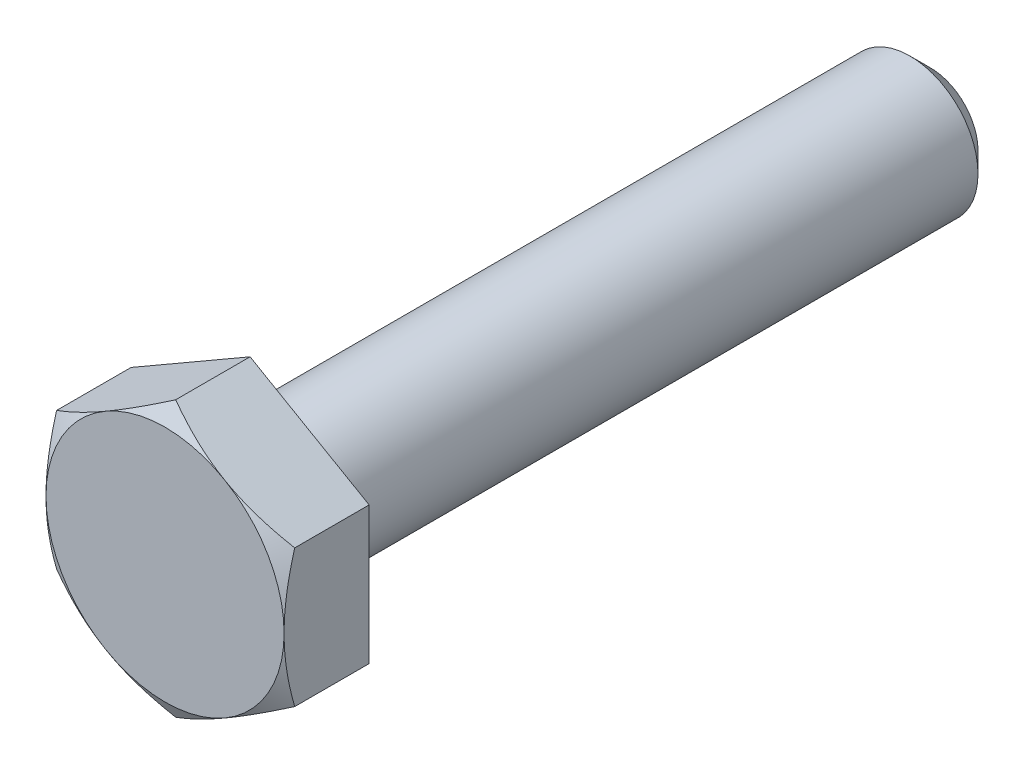
SolidWorks part; units mm, degrees
ref_plane "Front Plane" through (0, 0, 0) normal (0, 0, 1) x (1, 0, 0)
ref_plane "Top Plane" through (0, 0, 0) normal (0, 1, 0) x (1, 0, 0)
ref_plane "Right Plane" through (0, 0, 0) normal (1, 0, 0) x (0, 0, -1)
sketch "Sketch1" plane through (0, 0, 0) normal (1, 0, 0) x (0, 0, -1)
  line L0 (-17.8594, 0) -> (17.8594, 0) construction
  line L1 (-17.8594, 0) -> (-17.8594, 6.4158)
  line L2 (-17.8594, 6.4158) -> (-13.8906, 6.4158)
  line L3 (-13.8906, 6.4158) -> (-13.8906, 3.175)
  line L4 (-13.8906, 3.175) -> (17.8594, 3.175)
  line L5 (17.8594, 3.175) -> (17.8594, 0)
  line L6 (-17.8594, 5.5562) -> (-13.8906, 5.5562)
  line L7 (17.78, 3.3125) -> (18.415, 2.2126) construction
  line L8 (18.415, 2.2126) -> (19.05, 3.3125) construction
  line L9 (19.05, 3.3125) -> (17.78, 3.3125) construction
  line L10 (17.8594, 3.175) -> (18.9706, 3.175) construction
  line L11 (18.415, 3.3125) -> (18.415, 3.175) construction
  line L12 (18.415, 3.175) -> (18.415, 2.3501) construction
  line L13 (18.415, 2.3501) -> (18.415, 2.2126) construction
  line L14 (18.3356, 2.3501) -> (18.4944, 2.3501)
  line L15 (17.8197, 3.2437) -> (19.0103, 3.2437)
  line L16 (18.4944, 2.3501) -> (19.0103, 3.2437)
  line L17 (18.3356, 2.3501) -> (17.8197, 3.2437)
  line L18 (-13.8906, -3.175) -> (17.8594, -3.175) construction
  line L19 (-17.8594, -6.4158) -> (-13.8906, -6.4158) construction
  point P21 (18.415, 3.2437)
  point P25 (13.4144, -3.175)
  point P26 (-1.1906, 3.175)
  dimension "Length" = 31.75
  dimension "Head Height" = 3.9688
  dimension "Head Width" = 11.1125
  dimension "D5" = 12.8316
  dimension "Thread Pitch" = 1.27
  dimension "D7" = 0.1588
  dimension "Screw Size Decimal Equivalent" = 6.35
  dimension "D1" = 4.445
  dimension "Minimum Thread Length" = 19.05
ref_plane "Plane1" through (0, 0, 17.8594) normal (0, 0, 1) x (1, 0, 0)
sketch "Sketch2" plane through (0, 0, 17.8594) normal (0, 0, 1) x (1, 0, 0)
  line L0 (0, 4.2783) -> (0, 2.3892) construction
  line L1 (0, 6.4158) -> (-5.5562, 3.2079)
  line L2 (-5.5562, 3.2079) -> (-5.5562, -3.2079)
  line L3 (-5.5562, -3.2079) -> (0, -6.4158)
  line L4 (0, -6.4158) -> (5.5562, -3.2079)
  line L5 (5.5562, -3.2079) -> (5.5562, 3.2079)
  line L6 (5.5562, 3.2079) -> (0, 6.4158)
  line L9 (0.1667, 4.2783) -> (0.1667, 2.3892)
  line L10 (-0.1667, 4.2783) -> (-0.1667, 2.3892)
  circle A0 centre (0, 0) radius 5.5562 construction
  circle A1 centre (0, 0) radius 4.445 construction
  circle A2 centre (0, 0) radius 2.2225 construction
  arc A5 (0.1667, 4.2783) -> (-0.1667, 4.2783) centre (0, 4.2783) ccw
  arc A6 (-0.1667, 2.3892) -> (0.1667, 2.3892) centre (0, 2.3892) ccw
  point P14 (0, 3.3337)
  point P20 (0, 4.445)
  point P21 (0, 2.2225)
  dimension "D1" = 8.89
  dimension "D2" = 4.445
  dimension "D3" = 0.3334
ref_plane "Plane2" through (0, 0, 1.1906) normal (0, 0, 1) x (1, 0, 0)
sketch "Sketch3" plane through (0, 0, 0) normal (1, 0, 0) x (0, 0, -1)
  line L0 (17.8594, 3.175) -> (17.8594, 0) construction
  line L1 (-13.8906, 3.175) -> (17.8594, 3.175) construction
  line L2 (-13.8906, 6.4158) -> (-13.8906, 3.175) construction
  line L3 (-17.8594, 6.4158) -> (-13.8906, 6.4158) construction
  line L4 (-17.8594, 0) -> (-17.8594, 6.4158) construction
  line L5 (17.8594, 2.2225) -> (17.8594, 0)
  line L6 (-13.8906, 3.175) -> (16.9069, 3.175)
  line L7 (-13.8906, 6.4158) -> (-13.8906, 3.175)
  line L8 (-17.3631, 6.4158) -> (-13.8906, 6.4158)
  line L9 (-17.8594, 0) -> (-17.8594, 5.5562)
  line L10 (-17.8594, 0) -> (17.8594, 0) construction
  line L11 (-17.8594, 0) -> (17.8594, 0)
  line L12 (-17.8594, 5.5562) -> (-17.3631, 6.4158)
  line L14 (17.8594, 2.2225) -> (16.9069, 3.175)
  dimension "D1" = 30
  dimension "D2" = 45
  dimension "D3" = 0.9525
revolve "Revolve1" add sketch "Sketch3" angle 360 about L0
sketch "Sketch4" plane through (0, 0, 17.8594) normal (0, 0, 1) x (1, 0, 0)
  line L0 (5.5562, -3.2079) -> (5.5562, 3.2079) construction
  line L1 (0, -6.4158) -> (5.5562, -3.2079) construction
  line L2 (-5.5562, -3.2079) -> (0, -6.4158) construction
  line L3 (-5.5562, 3.2079) -> (-5.5562, -3.2079) construction
  line L4 (0, 6.4158) -> (-5.5562, 3.2079) construction
  line L5 (5.5562, 3.2079) -> (0, 6.4158) construction
  line L6 (5.5562, -3.2079) -> (5.5562, 3.2079)
  line L7 (0, -6.4158) -> (5.5562, -3.2079)
  line L8 (-5.5562, -3.2079) -> (0, -6.4158)
  line L9 (-5.5562, 3.2079) -> (-5.5562, -3.2079)
  line L10 (0, 6.4158) -> (-5.5562, 3.2079)
  line L11 (5.5562, 3.2079) -> (0, 6.4158)
extrude "Cut-Extrude1" cut sketch "Sketch4" against normal through all flip side to cut
sketch "Sketch9" plane through (0, 0, 17.8594) normal (0, 0, 1) x (1, 0, 0)
  line L0 (-0.1667, 4.2783) -> (-0.1667, 2.3892) construction
  line L1 (0.1667, 4.2783) -> (0.1667, 2.3892) construction
  line L2 (-0.1667, 4.2783) -> (-0.1667, 2.3892)
  line L3 (0.1667, 4.2783) -> (0.1667, 2.3892)
  arc A0 (0.1667, 4.2783) -> (-0.1667, 4.2783) centre (0, 4.2783) ccw construction
  arc A1 (-0.1667, 2.3892) -> (0.1667, 2.3892) centre (0, 2.3892) ccw construction
  arc A2 (0.1667, 4.2783) -> (-0.1667, 4.2783) centre (0, 4.2783) ccw
  arc A3 (-0.1667, 2.3892) -> (0.1667, 2.3892) centre (0, 2.3892) ccw
extrude "Cut-Extrude2" [suppressed] cut sketch "Sketch9" against normal blind 0.127
pattern_circular "CirPattern1" [suppressed] count 6 over 360 about axis through (0, 0, 17.8594) along (0, 0, -1) reverse direction yes of bodies 110
split "Split1" [suppressed] bodies to split 111
sketch "Sketch5" [suppressed] plane through (0, 0, -17.8594) normal (0, 0, -1) x (-1, 0, 0)
  circle A0 centre (0, 0) radius 3.175
curve "Helix/Spiral1" [suppressed] pitch 1.27 height 20.32 turns 16
sketch "Sketch6" [suppressed] plane through (0, 0, 0) normal (1, 0, 0) x (0, 0, -1)
  line L0 (18.3356, 2.3501) -> (18.4944, 2.3501) construction
  line L1 (18.3356, 2.3501) -> (17.8197, 3.2437) construction
  line L2 (17.8197, 3.2437) -> (19.0103, 3.2437) construction
  line L3 (18.4944, 2.3501) -> (19.0103, 3.2437) construction
  line L4 (18.3356, 2.3501) -> (18.4944, 2.3501)
  line L5 (18.3356, 2.3501) -> (17.8197, 3.2437)
  line L6 (17.8197, 3.2437) -> (19.0103, 3.2437)
  line L7 (18.4944, 2.3501) -> (19.0103, 3.2437)
sweep "Cut-Sweep1" [suppressed] cut profiles "Sketch6" path "Helix/Spiral1"
sketch "Sketch8" [suppressed] plane through (0, 0, 0) normal (1, 0, 0) x (0, 0, -1)
  line L0 (-1.1906, 3.175) -> (0.6425, 0)
  line L1 (-17.8594, 0) -> (17.8594, 0) construction
  line L2 (0.6425, 0) -> (-1.1906, 0)
  line L3 (-1.1906, 3.175) -> (-1.1906, 0)
  dimension "D1" = 60
revolve "Revolve2" [suppressed] add sketch "Sketch8" angle 360 about L0
equation "\"D5@Sketch1\"=\"Head Width@Sketch1\"*(2/sqr(3))"
equation "\"D7@Sketch1\" = \"Thread Pitch@Sketch1\" / 8"
equation "\"D1@Sketch2\"=\"Head Width@Sketch1\"*0.8"
equation "\"D2@Sketch2\"=\"Head Width@Sketch1\"*0.4"
equation "\"D3@Sketch2\"=\"Head Width@Sketch1\"*0.03"
equation "\"D3@Sketch3\"=\"Thread Pitch@Sketch1\"*0.75"
equation "\"D3@Helix/Spiral1\"=\"Minimum Thread Length@Sketch1\"+\"Thread Pitch@Sketch1\""
equation "\"D4@Helix/Spiral1\"=\"Thread Pitch@Sketch1\""
equation "\"D1@Sketch1\"=\"Thread Pitch@Sketch1\"*3.5"
